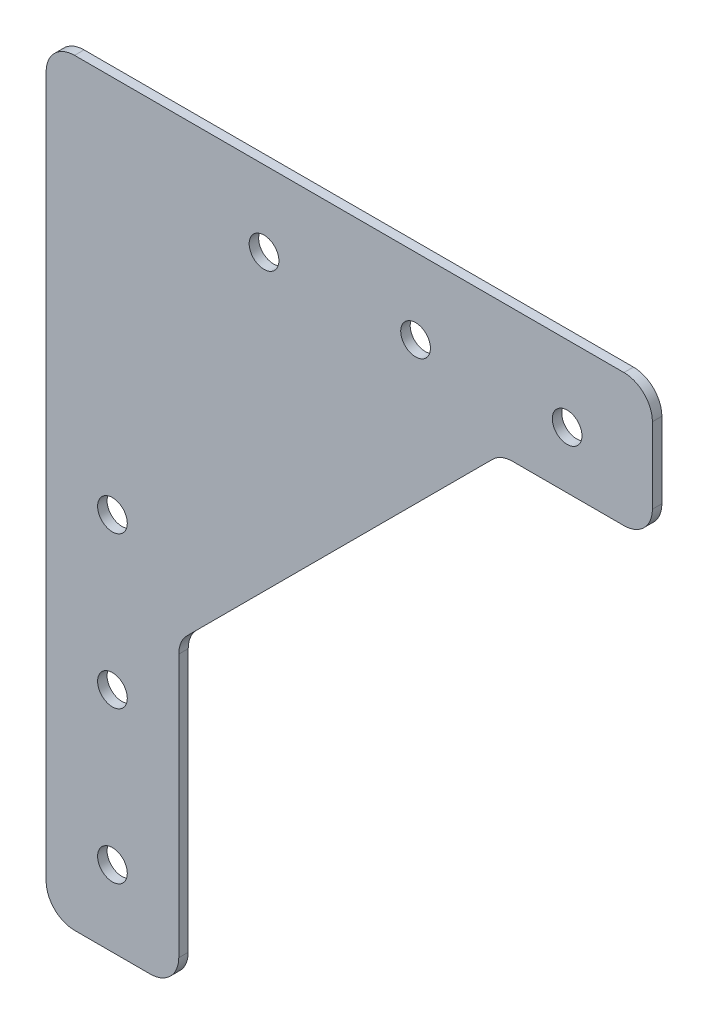
SolidWorks part; units mm, degrees
material "6061-T6 (SS)"
ref_plane "Front Plane" through (0, 0, 0) normal (0, 0, 1) x (1, 0, 0)
ref_plane "Top Plane" through (0, 0, 0) normal (0, 1, 0) x (1, 0, 0)
ref_plane "Right Plane" through (0, 0, 0) normal (1, 0, 0) x (0, 0, -1)
sketch "Sketch1" plane through (0, 0, 0) normal (0, 0, 1) x (1, 0, 0)
  line L8 (0, 0) -> (0, 127)
  line L14 (0, 127) -> (101.6, 127)
  line L15 (101.6, 127) -> (101.6, 104.775)
  line L17 (22.225, 0) -> (0, 0)
  line L18 (11.1125, 0) -> (11.1125, 127) construction
  line L19 (22.225, 0) -> (22.225, 50.8)
  line L20 (22.225, 50.8) -> (76.2, 104.775)
  line L21 (76.2, 104.775) -> (101.6, 104.775)
  circle A7 centre (11.1125, 63.5) radius 2.4892
  circle A8 centre (11.1125, 38.1) radius 2.4892
  circle A9 centre (11.1125, 12.7) radius 2.4892
  circle A11 centre (87.3125, 114.3) radius 2.4892
  circle A12 centre (61.9125, 114.3) radius 2.4892
  circle A13 centre (36.5125, 114.3) radius 2.4892
  dimension "D5" = 4.9784
  dimension "D7" = 12.7
  dimension "D1" = 22.225
  dimension "D2" = 127
  dimension "D3" = 101.6
  dimension "D4" = 3
  dimension "D6" = 25.4
  dimension "D8" = 3
  dimension "D9" = 12.7
  dimension "D10" = 25.4
  dimension "D11" = 25.4
  dimension "D12" = 45
  dimension "D13" = 25.4
extrude "Boss-Extrude1" add sketch "Sketch1" along normal mid plane 1.5875 contours L18 A7 | A7 L18 | L18 A9 | A9 L18 | A11 | L8 L14 L15 L21 L20 L19 L17 | A8 | A12 | A13 region at (10.0561, 12.7, 0) region at (12.1689, 12.7, 0) region at (12.1689, 63.5, 0) region at (10.0561, 63.5, 0) region at (87.3125, 114.3, 0)
fillet "Fillet1" radius 4.7625 7 edges at (0, 127, 0) (0, 0, 0) (101.6, 104.775, 0) (76.2, 104.775, 0) (22.225, 50.8, 0) (22.225, 0, 0) (101.6, 127, 0)
